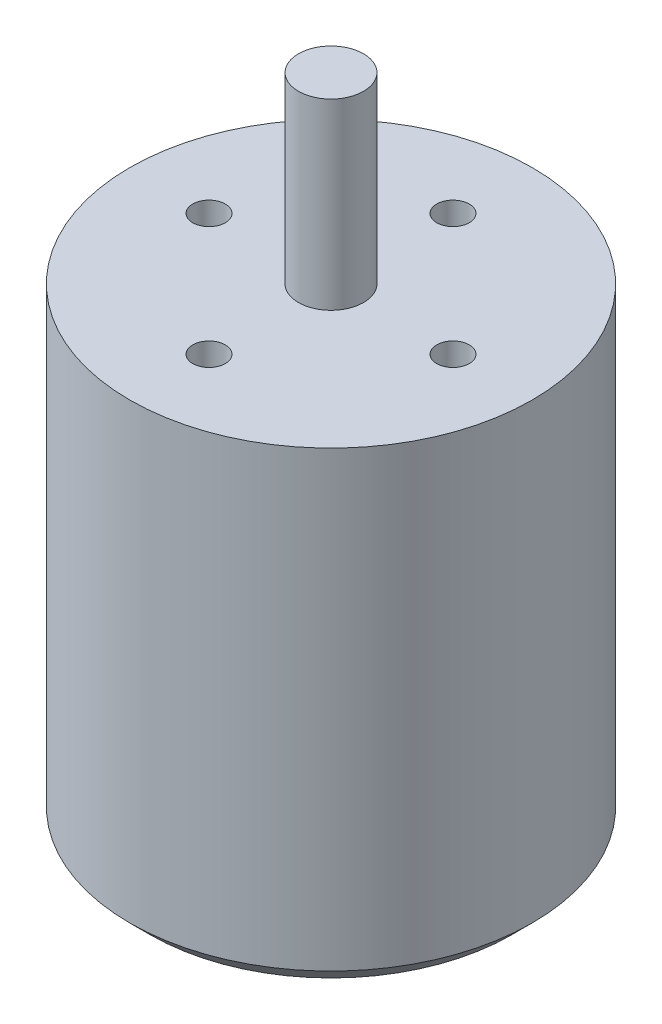
SolidWorks part; units mm, degrees
ref_plane "Front Plane" through (0, 0, 0) normal (0, 0, 1) x (1, 0, 0)
ref_plane "Top Plane" through (0, 0, 0) normal (0, 1, 0) x (1, 0, 0)
ref_plane "Right Plane" through (0, 0, 0) normal (1, 0, 0) x (0, 0, -1)
sketch "Sketch1" plane through (0, 0, 0) normal (0, 1, 0) x (1, 0, 0)
  circle A0 centre (0, 0) radius 24.75
  dimension "D1" = 49.5
extrude "Boss-Extrude1" add sketch "Sketch1" along normal blind 58.2
sketch "Sketch2" plane through (0, 58.2, 0) normal (0, 1, 0) x (1, 0, 0)
  circle A0 centre (0, 0) radius 4
  dimension "D1" = 8
extrude "Boss-Extrude2" add sketch "Sketch2" along normal blind 22.5
chamfer "Chamfer1" distance 2.5 angle 45 1 edges at (0, 0, 24.75)
sketch "Sketch3" plane through (0, 0, 0) normal (0, -1, 0) x (1, 0, 0)
  circle A0 centre (0, 0) radius 6.8
  dimension "D1" = 13.6
extrude "Boss-Extrude3" add sketch "Sketch3" along normal blind 2
fillet "Fillet1" radius 0.5 1 edges at (0, 0, -6.8)
sketch "Sketch4" plane through (0, 58.2, 0) normal (0, 1, 0) x (1, 0, 0)
  circle A0 centre (0, 0) radius 15 construction
  circle A1 centre (0, 15) radius 2
  circle A2 centre (15, 0) radius 2
  circle A3 centre (0, -15) radius 2
  circle A4 centre (-15, 0) radius 2
  point P3 (0, 15)
  point P4 (-15, 0)
  point P5 (0, -15)
  point P6 (15, 0)
  dimension "D1" = 30
  dimension "D2" = 4
extrude "Cut-Extrude1" cut sketch "Sketch4" against normal blind 10
sketch "Sketch5" plane through (0, 0, 0) normal (0, -1, 0) x (1, 0, 0)
  circle A0 centre (0, 0) radius 9.875 construction
  circle A1 centre (0, 9.875) radius 1.5
  circle A2 centre (9.875, 0) radius 1.5
  circle A3 centre (0, -9.875) radius 1.5
  circle A4 centre (-9.875, 0) radius 1.5
  dimension "D1" = 19.75
  dimension "D2" = 3
extrude "Cut-Extrude2" cut sketch "Sketch5" against normal blind 5
